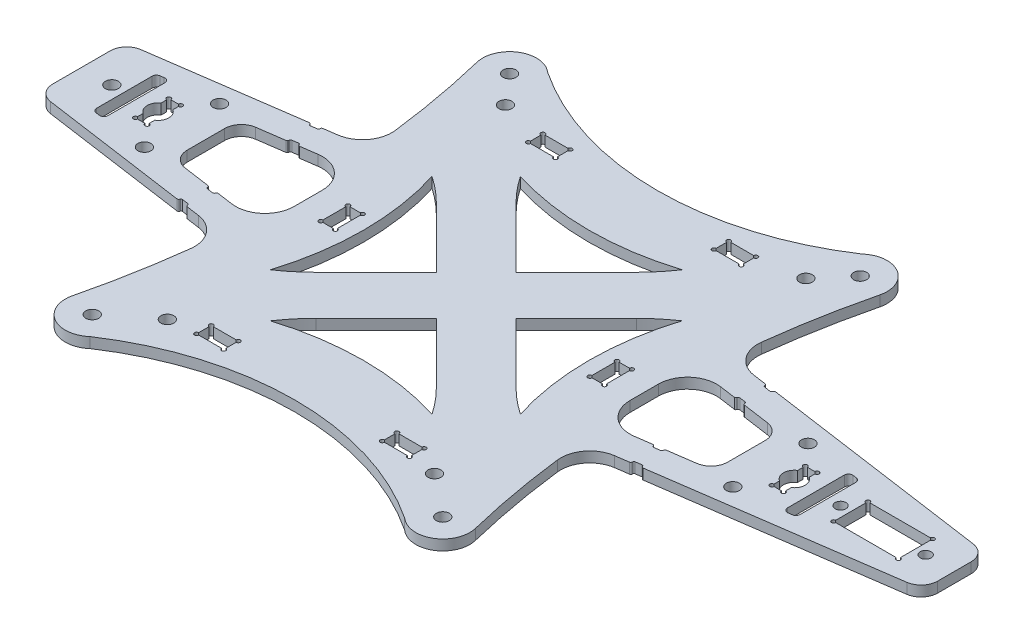
SolidWorks part; units mm, degrees
material "PPS"
ref_plane "前视基准面" through (0, 0, 0) normal (0, 0, 1) x (1, 0, 0)
ref_plane "上视基准面" through (0, 0, 0) normal (0, 1, 0) x (1, 0, 0)
ref_plane "右视基准面" through (0, 0, 0) normal (1, 0, 0) x (0, 0, -1)
sketch "草图1" plane through (0, 0, 0) normal (0, 1, 0) x (1, 0, 0)
  line L3 (-133.7177, 0) -> (146.3754, 0) construction
  line L56 (0, 96.0639) -> (0, -115.1457) construction
  line L65 (-25.5, 41.5) -> (-19, 41.5)
  line L66 (-34, 3.25) -> (-30.5, 3.25)
  line L70 (-34, 3.25) -> (-34, -3.25)
  line L76 (-34, -3.25) -> (-30.5, -3.25)
  line L80 (-30.5, 3.25) -> (-30.5, -3.25)
  line L81 (-25.5, -38) -> (-19, -38)
  line L82 (-25.5, -38) -> (-25.5, -41.5)
  line L83 (-25.5, -41.5) -> (-19, -41.5)
  line L84 (-19, -38) -> (-19, -41.5)
  line L85 (-19, 38) -> (-19, 41.5)
  line L86 (-25.5, 38) -> (-19, 38)
  line L142 (-25.5, 38) -> (-25.5, 41.5)
  line L143 (25.5, 38) -> (25.5, 41.5)
  line L144 (25.5, 38) -> (19, 38)
  line L145 (19, 38) -> (19, 41.5)
  line L146 (19, -38) -> (19, -41.5)
  line L147 (25.5, -41.5) -> (19, -41.5)
  line L148 (25.5, -38) -> (25.5, -41.5)
  line L149 (25.5, -38) -> (19, -38)
  line L150 (30.5, 3.25) -> (30.5, -3.25)
  line L151 (34, -3.25) -> (30.5, -3.25)
  line L152 (34, 3.25) -> (34, -3.25)
  line L153 (34, 3.25) -> (30.5, 3.25)
  line L154 (25.5, 41.5) -> (19, 41.5)
  line L155 (77.65, -2.1518) -> (77.65, -4)
  line L156 (74.85, 4) -> (77.65, 4)
  line L157 (74.85, 4) -> (74.85, 2.1768)
  line L158 (74.85, -4) -> (77.65, -4)
  line L159 (77.65, 4) -> (77.65, 2.1518)
  line L160 (74.85, -2.1768) -> (74.85, -4)
  line L161 (97.5, 7.6653) -> (97.5, -9.1503) construction
  line L162 (89.75, 4.1) -> (105.25, 4.1)
  line L163 (89.75, 4.1) -> (89.75, -4.1)
  line L164 (89.75, -4.1) -> (105.25, -4.1)
  line L165 (105.25, 4.1) -> (105.25, -4.1)
  line L166 (-97.5, 7.6653) -> (-97.5, -9.1503) construction
  line L171 (-74.85, -2.1768) -> (-74.85, -4)
  line L172 (-77.65, 4) -> (-77.65, 2.1518)
  line L173 (-74.85, -4) -> (-77.65, -4)
  line L174 (-74.85, 4) -> (-74.85, 2.1768)
  line L175 (-74.85, 4) -> (-77.65, 4)
  line L176 (-77.65, -2.1518) -> (-77.65, -4)
  line L177 (114.5911, 7.4683) -> (114.5911, -7.4683)
  line L178 (114.5911, 7.4683) -> (43.1936, 17.6463)
  line L179 (114.5911, -7.4683) -> (43.1936, -17.6463)
  line L183 (-23.978, 14.4296) -> (-9.5485, 0)
  line L184 (14.4296, 23.978) -> (0, 9.5485)
  line L185 (-23.978, -14.4296) -> (-9.5485, 0)
  line L186 (-14.4296, 23.978) -> (0, 9.5485)
  line L187 (23.978, -14.4296) -> (9.5485, 0)
  line L188 (23.978, 14.4296) -> (9.5485, 0)
  line L189 (-14.4296, -23.978) -> (0, -9.5485)
  line L190 (14.4296, -23.978) -> (0, -9.5485)
  line L191 (-94.5795, 10.321) -> (-94.5795, -10.321)
  line L192 (-43.1936, 17.6463) -> (-94.5795, 10.321)
  line L193 (-94.5795, -10.321) -> (-43.1936, -17.6463)
  line L195 (-64.75, -7.9571) -> (-64.75, 7.9571)
  line L196 (-64.75, 7.9571) -> (-40.25, 11.4497)
  line L197 (-40.25, 11.4497) -> (-40.25, -11.4497)
  line L198 (-64.75, -7.9571) -> (-40.25, -11.4497)
  line L199 (64.75, 7.9571) -> (40.25, 11.4497)
  line L200 (40.25, 11.4497) -> (40.25, -11.4497)
  line L201 (64.75, -7.9571) -> (40.25, -11.4497)
  line L202 (64.75, 7.9571) -> (64.75, -7.9571)
  line L203 (84.3, 7.5437) -> (81.4, 7.9571)
  line L204 (81.4, 7.9571) -> (81.4, -7.9571)
  line L205 (84.3, -7.5437) -> (81.4, -7.9571)
  line L206 (84.3, 7.5437) -> (84.3, -7.5437)
  line L207 (-84.3, 7.5437) -> (-84.3, -7.5437)
  line L208 (-84.3, -7.5437) -> (-81.4, -7.9571)
  line L209 (-81.4, 7.9571) -> (-81.4, -7.9571)
  line L210 (-84.3, 7.5437) -> (-81.4, 7.9571)
  circle A0 centre (-36, 43) radius 1.55
  circle A1 centre (-32, -42) radius 1.55
  circle A2 centre (32, -42) radius 1.55
  circle A3 centre (36, 43) radius 1.55
  circle A4 centre (42, 50) radius 1.55
  circle A5 centre (42, -50) radius 1.55
  circle A6 centre (-42, -50) radius 1.55
  circle A7 centre (-42, 50) radius 1.55
  arc A8 (74.85, 2.1768) -> (74.85, -2.1768) centre (76.2307, 0) ccw
  arc A9 (77.65, -2.1518) -> (77.65, 2.1518) centre (76.2307, 0) ccw
  circle A10 centre (107.7, 0) radius 1.3
  circle A11 centre (87.3, 0) radius 1.3
  circle A12 centre (-87.3, 0) radius 1.3 construction
  arc A14 (-77.65, -2.1518) -> (-77.65, 2.1518) centre (-76.2307, 0) cw
  arc A15 (-74.85, 2.1768) -> (-74.85, -2.1768) centre (-76.2307, 0) cw
  arc A18 (-37.7098, 54.831) -> (37.7098, 54.831) centre (0, 111.5317) ccw
  arc A20 (48.2756, 48.4632) -> (43.1936, 17.6463) centre (246.1791, 0) ccw
  arc A21 (48.2756, 48.4632) -> (37.7098, 54.831) centre (42, 50) ccw
  arc A22 (-37.7098, -54.831) -> (37.7098, -54.831) centre (0, -111.5317) cw
  arc A23 (48.2756, -48.4632) -> (43.1936, -17.6463) centre (246.1791, 0) cw
  arc A24 (48.2756, -48.4632) -> (37.7098, -54.831) centre (42, -50) cw
  arc A26 (-48.2756, -48.4632) -> (-37.7098, -54.831) centre (-42, -50) ccw
  arc A27 (-48.2756, -48.4632) -> (-43.1936, -17.6463) centre (-246.1791, 0) ccw
  arc A28 (-48.2756, 48.4632) -> (-37.7098, 54.831) centre (-42, 50) cw
  arc A30 (-48.2756, 48.4632) -> (-43.1936, 17.6463) centre (-246.1791, 0) cw
  arc A31 (-23.978, 14.4296) -> (-29.9602, 19.3706) centre (-52.8883, -14.4807) ccw
  arc A32 (-23.978, -14.4296) -> (-29.9602, -19.3706) centre (-52.8883, 14.4807) cw
  arc A33 (-29.9602, -19.3706) -> (-29.9602, 19.3706) centre (-91.9966, 0) ccw
  arc A34 (-14.4296, 23.978) -> (-19.3706, 29.9602) centre (14.4807, 52.8883) cw
  arc A35 (-19.3706, 29.9602) -> (19.3706, 29.9602) centre (0, 91.9966) ccw
  arc A36 (14.4296, 23.978) -> (19.3706, 29.9602) centre (-14.4807, 52.8883) ccw
  arc A37 (23.978, 14.4296) -> (29.9602, 19.3706) centre (52.8883, -14.4807) cw
  arc A38 (29.9602, 19.3706) -> (29.9602, -19.3706) centre (91.9966, 0) ccw
  arc A39 (23.978, -14.4296) -> (29.9602, -19.3706) centre (52.8883, 14.4807) ccw
  arc A40 (14.4296, -23.978) -> (19.3706, -29.9602) centre (-14.4807, -52.8883) cw
  arc A41 (19.3706, -29.9602) -> (-19.3706, -29.9602) centre (0, -91.9966) ccw
  arc A42 (-14.4296, -23.978) -> (-19.3706, -29.9602) centre (14.4807, -52.8883) ccw
  circle A43 centre (70.5, 9) radius 1.55
  circle A44 centre (70.5, -9) radius 1.55
  circle A45 centre (-70.5, -9) radius 1.55
  circle A46 centre (-70.5, 9) radius 1.55
  circle A47 centre (-87.3, 0) radius 1.55
  point P81 (-34, 0)
  point P118 (0, 0)
  point P140 (-40.25, 0)
  point P148 (0, 0)
  point P149 (-64.75, 0)
  point P154 (0, 0)
  point P155 (0, 0)
  point P156 (0, 0)
  point P157 (0, 0)
  point P158 (0, 0)
  dimension "D5" = 38
  dimension "D18" = 8.2
  dimension "D24" = 3.1
  dimension "D6" = 3.1
  dimension "D11" = 50
  dimension "D15" = 74.85
  dimension "D16" = 2.6
  dimension "D17" = 15.5
  dimension "D21" = 3.1
  dimension "D1" = 6.5
  dimension "D2" = 3.5
  dimension "D3" = 30.5
  dimension "D4" = 19
  dimension "D7" = 32
  dimension "D8" = 42
  dimension "D9" = 43
  dimension "D10" = 36
  dimension "D12" = 42
  dimension "D13" = 2.8
  dimension "D14" = 4
  dimension "D19" = 2.45
  dimension "D20" = 97.5
  dimension "D22" = 9
  dimension "D23" = 70.5
  dimension "D25" = 6.55
  dimension "D26" = 5.75
  dimension "D27" = 6.25
  dimension "D28" = 4
  dimension "D29" = 2.45
  dimension "D30" = 3
  dimension "D31" = 3.75
extrude "凸台-拉伸1" add sketch "草图1" along normal blind 2.5
fillet "圆角1" radius 4 8 edges at (114.5911, 1.25, -7.4683) (114.5911, 1.25, 7.4683) (-94.5795, 1.25, 10.321) (-94.5795, 1.25, -10.321) (-64.75, 1.25, 7.9571) (-64.75, 1.25, -7.9571) (64.75, 1.25, 7.9571) (64.75, 1.25, -7.9571)
fillet "圆角2" radius 7 8 edges at (43.1936, 1.25, -17.6463) (43.1936, 1.25, 17.6463) (-43.1936, 1.25, 17.6463) (-43.1936, 1.25, -17.6463) (40.25, 1.25, 11.4497) (40.25, 1.25, -11.4497) (-40.25, 1.25, 11.4497) (-40.25, 1.25, -11.4497)
sketch "草图6" plane through (0, 2.5, 0) normal (0, 1, 0) x (1, 0, 0)
  line L0 (53.296, 16.2062) -> (55.6373, 15.8724)
  line L1 (111.1557, 7.958) -> (49.8638, 16.6954) construction
  line L2 (55.6373, 15.8724) -> (55.2455, 15.2717)
  line L3 (55.2455, 15.2717) -> (53.296, 15.5496)
  line L4 (53.296, 15.5496) -> (53.296, 16.2062)
  line L5 (56.9219, 15.6893) -> (55.9975, 9.2048) construction
  line L6 (61.3145, 8.4469) -> (48.2379, 10.311) construction
  line L7 (56.4597, 12.447) -> (48.7761, 13.5424) construction
  line L8 (54.5046, 10.0742) -> (52.555, 10.3521)
  line L9 (54.7129, 9.3879) -> (54.5046, 10.0742)
  line L10 (52.3716, 9.7217) -> (54.7129, 9.3879)
  line L11 (52.555, 10.3521) -> (52.3716, 9.7217)
  line L12 (0, 0) -> (132.6638, 0) construction
  line L13 (52.555, -10.3521) -> (52.3716, -9.7217)
  line L14 (52.3716, -9.7217) -> (54.7129, -9.3879)
  line L15 (54.7129, -9.3879) -> (54.5046, -10.0742)
  line L16 (54.5046, -10.0742) -> (52.555, -10.3521)
  line L17 (53.296, -15.5496) -> (53.296, -16.2062)
  line L18 (55.2455, -15.2717) -> (53.296, -15.5496)
  line L19 (55.6373, -15.8724) -> (55.2455, -15.2717)
  line L20 (53.296, -16.2062) -> (55.6373, -15.8724)
  line L21 (0, -0.7474) -> (0, 57.4396) construction
  line L22 (-53.296, -16.2062) -> (-55.6373, -15.8724)
  line L23 (-55.6373, -15.8724) -> (-55.2455, -15.2717)
  line L24 (-55.2455, -15.2717) -> (-53.296, -15.5496)
  line L25 (-53.296, -15.5496) -> (-53.296, -16.2062)
  line L26 (-54.5046, -10.0742) -> (-52.555, -10.3521)
  line L27 (-54.7129, -9.3879) -> (-54.5046, -10.0742)
  line L28 (-52.3716, -9.7217) -> (-54.7129, -9.3879)
  line L29 (-52.555, -10.3521) -> (-52.3716, -9.7217)
  line L30 (-52.555, 10.3521) -> (-52.3716, 9.7217)
  line L31 (-52.3716, 9.7217) -> (-54.7129, 9.3879)
  line L32 (-54.7129, 9.3879) -> (-54.5046, 10.0742)
  line L33 (-54.5046, 10.0742) -> (-52.555, 10.3521)
  line L34 (-53.296, 15.5496) -> (-53.296, 16.2062)
  line L35 (-55.2455, 15.2717) -> (-53.296, 15.5496)
  line L36 (-55.6373, 15.8724) -> (-55.2455, 15.2717)
  line L37 (-53.296, 16.2062) -> (-55.6373, 15.8724)
  dimension "D1" = 65
  dimension "D2" = 0.65
extrude "切除-拉伸3" cut sketch "草图6" against normal through all
fillet "圆角5" radius 0.35 32 edges at (-55.6373, 1.25, -15.8724) (-55.2455, 1.25, -15.2717) (-53.296, 1.25, -15.5496) (-53.296, 1.25, -16.2062) (-52.3716, 1.25, 9.7217) (-52.555, 1.25, 10.3521) (-54.5046, 1.25, 10.0742) (-54.7129, 1.25, 9.3879) (-52.3716, 1.25, -9.7217) (-52.555, 1.25, -10.3521) (-54.7129, 1.25, -9.3879) (-54.5046, 1.25, -10.0742) (-53.296, 1.25, 16.2062) (-53.296, 1.25, 15.5496) (-55.2455, 1.25, 15.2717) (-55.6373, 1.25, 15.8724) (55.6373, 1.25, 15.8724) (55.2455, 1.25, 15.2717) (53.296, 1.25, 15.5496) (53.296, 1.25, 16.2062) (54.7129, 1.25, 9.3879) (54.5046, 1.25, 10.0742) (52.555, 1.25, 10.3521) (52.3716, 1.25, 9.7217) (54.7129, 1.25, -9.3879) (54.5046, 1.25, -10.0742) (52.3716, 1.25, -9.7217) (52.555, 1.25, -10.3521) (55.2455, 1.25, -15.2717) (53.296, 1.25, -15.5496) (55.6373, 1.25, -15.8724) (53.296, 1.25, -16.2062)
fillet "圆角4" radius 1 8 edges at (-81.4, 1.25, 7.9571) (-84.3, 1.25, 7.5437) (-84.3, 1.25, -7.5437) (-81.4, 1.25, -7.9571) (81.4, 1.25, 7.9571) (84.3, 1.25, 7.5437) (84.3, 1.25, -7.5437) (81.4, 1.25, -7.9571)
sketch "草图2" plane through (0, 2.5, 0) normal (0, 1, 0) x (1, 0, 0)
  line L0 (0, 0) -> (0, -66.7571) construction
  circle A0 centre (-77.65, 4) radius 0.5
  circle A1 centre (-74.85, 4) radius 0.5
  circle A2 centre (-77.65, -4) radius 0.5
  circle A3 centre (-74.85, -4) radius 0.5
  circle A4 centre (-25.5, 41.5) radius 0.5
  circle A5 centre (-19, 41.5) radius 0.5
  circle A6 centre (-25.5, 38) radius 0.5
  circle A7 centre (-19, 38) radius 0.5
  circle A8 centre (-34, 3.25) radius 0.5
  circle A9 centre (-30.5, 3.25) radius 0.5
  circle A10 centre (-34, -3.25) radius 0.5
  circle A11 centre (-30.5, -3.25) radius 0.5
  circle A12 centre (-25.5, -38) radius 0.5
  circle A13 centre (-19, -38) radius 0.5
  circle A14 centre (-25.5, -41.5) radius 0.5
  circle A15 centre (-19, -41.5) radius 0.5
  circle A16 centre (19, -41.5) radius 0.5
  circle A17 centre (25.5, -41.5) radius 0.5
  circle A18 centre (19, -38) radius 0.5
  circle A19 centre (25.5, -38) radius 0.5
  circle A20 centre (30.5, -3.25) radius 0.5
  circle A21 centre (34, -3.25) radius 0.5
  circle A22 centre (30.5, 3.25) radius 0.5
  circle A23 centre (34, 3.25) radius 0.5
  circle A24 centre (19, 38) radius 0.5
  circle A25 centre (25.5, 38) radius 0.5
  circle A26 centre (19, 41.5) radius 0.5
  circle A27 centre (25.5, 41.5) radius 0.5
  circle A28 centre (74.85, -4) radius 0.5
  circle A29 centre (77.65, -4) radius 0.5
  circle A30 centre (74.85, 4) radius 0.5
  circle A31 centre (77.65, 4) radius 0.5
  circle A32 centre (89.75, 4.1) radius 0.5
  circle A33 centre (105.25, 4.1) radius 0.5
  circle A34 centre (89.75, -4.1) radius 0.5
  circle A35 centre (105.25, -4.1) radius 0.5
  dimension "D1" = 1
extrude "直角约束" cut sketch "草图2" against normal through all
